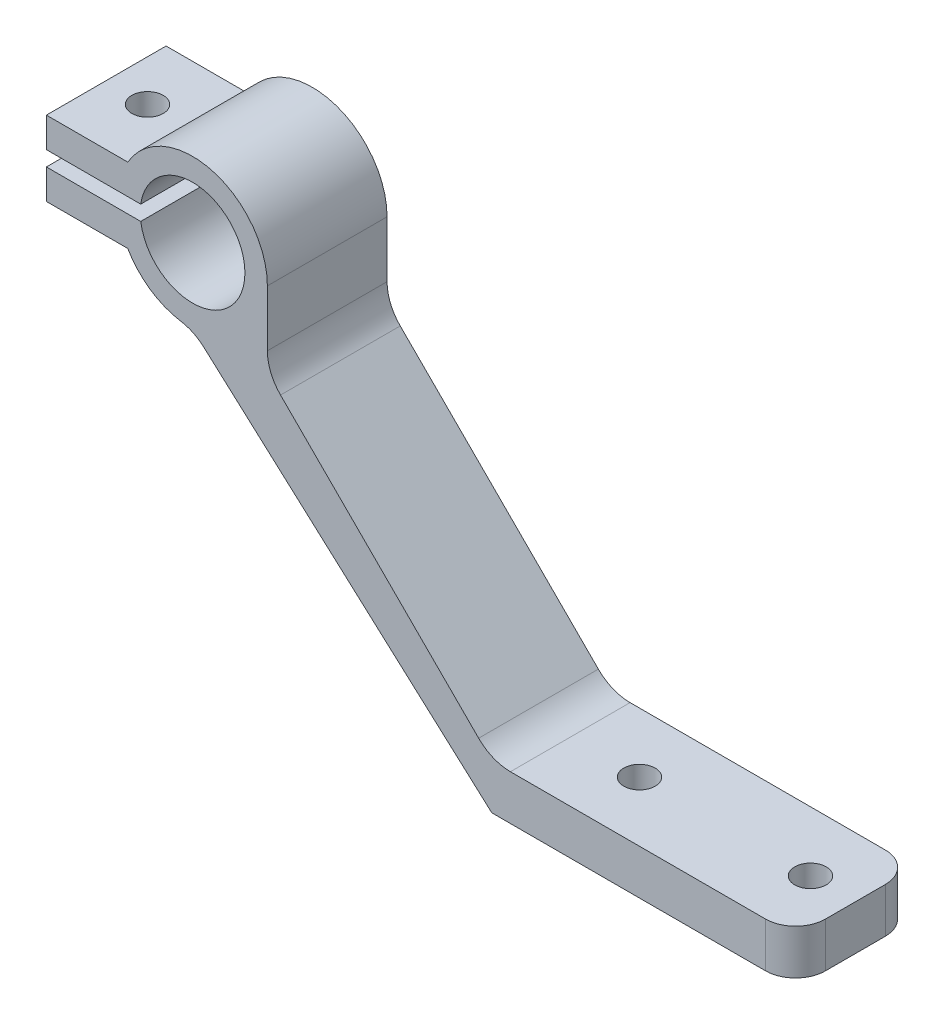
SolidWorks part; units mm, degrees
ref_plane "Front Plane" through (0, 0, 0) normal (0, 0, 1) x (1, 0, 0)
ref_plane "Top Plane" through (0, 0, 0) normal (0, 1, 0) x (1, 0, 0)
ref_plane "Right Plane" through (0, 0, 0) normal (1, 0, 0) x (0, 0, -1)
sketch "Sketch1" plane through (0, 0, 0) normal (0, 1, 0) x (1, 0, 0)
  line L0 (-5.715, 0) -> (5.715, 0)
  line L1 (-6.715, -4) -> (6.715, -4)
  line L2 (-8.715, -2) -> (-8.715, 2) construction
  line L3 (-6.715, 4) -> (6.715, 4)
  line L4 (8.715, -2) -> (8.715, 2)
  line L5 (-8.715, -4) -> (8.715, 4) construction
  line L6 (-8.715, 4) -> (8.715, -4) construction
  line L7 (-6.715, 4) -> (-11.585, 4)
  line L8 (-11.585, 4) -> (-11.585, -4)
  line L9 (-11.585, -4) -> (-6.715, -4)
  circle A0 centre (-5.715, 0) radius 1.05
  circle A1 centre (5.715, 0) radius 1.05
  arc A2 (6.715, 4) -> (8.715, 2) centre (6.715, 2) cw
  arc A3 (6.715, -4) -> (8.715, -2) centre (6.715, -2) ccw
  arc A4 (-6.715, -4) -> (-7.8876, -3.6202) centre (-6.715, -2) cw construction
  arc A5 (-7.8876, 3.6202) -> (-6.715, 4) centre (-6.715, 2) cw construction
  arc A6 (-8.715, 2) -> (-7.8876, 3.6202) centre (-6.715, 2) cw construction
  arc A7 (-7.8876, -3.6202) -> (-8.715, -2) centre (-6.715, -2) cw construction
  point P0 (0, 0)
  dimension "D4" = 2.1
  dimension "D5" = 2
  dimension "D1" = 3
  dimension "D2" = 4
  dimension "D3" = 11.43
  dimension "D6" = 5.87
extrude "Boss-Extrude1" add sketch "Sketch1" along normal blind 3 contours A5 L2 A4 L1 A3 L4 A2 L3 A1 A0 region at (-9.15, 0, 3.7818)
sketch "Sketch3" plane through (0, 0, 0) normal (0, 0, 1) x (1, 0, 0)
  line L2 (-41.3547, 21.5) -> (-36.3547, 21.5) construction
  line L3 (-41.3547, 21.5) -> (-41.3547, 22.5)
  line L4 (-36.3547, 21.5) -> (-36.3547, 22.5) construction
  line L5 (-41.3547, 24.5) -> (-36.3547, 24.5) construction
  line L6 (-41.3547, 21.5) -> (-36.3547, 24.5) construction
  line L7 (-36.3547, 21.5) -> (-41.3547, 24.5) construction
  line L8 (-41.3547, 25.5) -> (-36.3547, 25.5)
  line L9 (-41.3547, 22.5) -> (-36.3547, 22.5)
  line L10 (-41.3547, 23.5) -> (-36.3547, 23.5)
  line L11 (-41.3547, 20.5) -> (-36.3547, 20.5)
  line L12 (-36.3547, 20.5) -> (-35.9151, 20.5)
  line L13 (-41.3547, 20.5) -> (-41.3547, 21.5)
  line L14 (-41.3547, 24.5) -> (-41.3547, 25.5)
  line L15 (-36.3547, 25.5) -> (-35.9151, 25.5)
  line L16 (-36.3547, 23.5) -> (-35.0491, 23.5)
  line L17 (-36.3547, 22.5) -> (-35.0491, 22.5)
  line L18 (-41.3547, 22.5) -> (-41.3547, 23.5) construction
  line L19 (-41.3547, 23.5) -> (-41.3547, 24.5)
  line L20 (-36.3547, 22.5) -> (-36.3547, 23.5) construction
  line L21 (-36.3547, 23.5) -> (-36.3547, 24.5) construction
  line L22 (-26.585, 23) -> (-26.585, 18)
  line L23 (-26.585, 18) -> (-31.585, 18)
  arc A0 (-35.9151, 20.5) -> (-31.585, 18) centre (-31.585, 23) ccw
  circle A1 centre (-31.585, 23) radius 3.5
  arc A2 (-36.5599, 23.5) -> (-36.5599, 22.5) centre (-31.585, 23) ccw construction
  arc A3 (-36.5599, 22.5) -> (-36.3547, 21.5) centre (-31.585, 23) ccw construction
  arc A4 (-36.3547, 21.5) -> (-35.9151, 20.5) centre (-31.585, 23) ccw construction
  arc A5 (-36.3547, 24.5) -> (-36.5599, 23.5) centre (-31.585, 23) ccw construction
  arc A6 (-35.9151, 25.5) -> (-36.3547, 24.5) centre (-31.585, 23) ccw construction
  arc A7 (-31.585, 18) -> (-26.585, 23) centre (-31.585, 23) ccw construction
  arc A8 (-26.585, 23) -> (-35.9151, 25.5) centre (-31.585, 23) ccw
  point P6 (-38.8547, 23)
  dimension "D1" = 7
  dimension "D2" = 1.5
  dimension "D3" = 20
  dimension "D4" = 20
  dimension "D5" = 3
  dimension "D6" = 5
  dimension "D7" = 1
  dimension "D8" = 1
extrude "Boss-Extrude2" add sketch "Sketch3" along normal blind 4 and the other way blind 4 separate body contours A0 A1 region at (-41.1763, 22, 0)
loft "Loft2" add section face at (-29.085, 18, 0) section face at (-11.585, 1.5, 0) connector at (-26.585, 18, -4) connector at (-11.585, 3, -4)
fillet "Fillet1" radius 3 3 edges at (-11.585, 3, 0)
sketch "Sketch5" plane through (-4.2925, -4.2925, 0) normal (0.7071, 0.7071, 0) x (0, 0, -1)
  line L0 (0, 30.2837) -> (0, 11.5558)
  line L1 (4, 30.2837) -> (-4, 30.2837) construction
  line L2 (-4, 11.5558) -> (4, 11.5558) construction
ref_plane "Plane1" through (0, 0, 0) normal (0, 0, 1) x (0.7071, -0.7071, 0)
sketch "Sketch7" plane through (0, 0, 0) normal (0, 0, 1) x (0.7071, -0.7071, 0)
  line L0 (-35.0619, -2.535) -> (-8.3191, -4.0765)
  line L1 (-9.4345, -5.1918) -> (2.6269, 6.8695) construction
  line L2 (-5.42, -1.1773) -> (-6.9049, -2.6623) construction
  line L3 (-5.42, -1.1773) -> (-6.9049, -2.6623) construction
  arc A0 (-35.0619, -2.535) -> (-43.4271, -7.3646) centre (-38.5974, -6.0705) ccw construction
  dimension "D1" = 2
rib "Rib5" [suppressed] sketch "Sketch7" sketch "Sketch7" thickness 2 extrusion direction parallel to sketch draft on yes draft angle 10 parameters "D1"=2, "D3"=10
sketch "Sketch8" plane through (0, 25.5, 0) normal (0, 1, 0) x (1, 0, 0)
  circle A0 centre (-38.5942, 0) radius 1.05
  dimension "D1" = 2.1
extrude "Cut-Extrude1" cut sketch "Sketch8" against normal through all both and the other way through all
sketch "Sketch9" plane through (0, 20.5, 0) normal (0, -1, 0) x (1, 0, 0)
  line L1 (-36.5942, 1.1547) -> (-38.5942, 2.3094)
  line L2 (-38.5942, 2.3094) -> (-40.5942, 1.1547)
  line L3 (-40.5942, 1.1547) -> (-40.5942, -1.1547)
  line L4 (-40.5942, -1.1547) -> (-38.5942, -2.3094)
  line L5 (-38.5942, -2.3094) -> (-36.5942, -1.1547)
  line L6 (-36.5942, -1.1547) -> (-36.5942, 1.1547)
  circle A0 centre (-38.5942, 0) radius 2 construction
  dimension "D1" = 4
extrude "Cut-Extrude2" cut sketch "Sketch9" against normal blind 0.8
